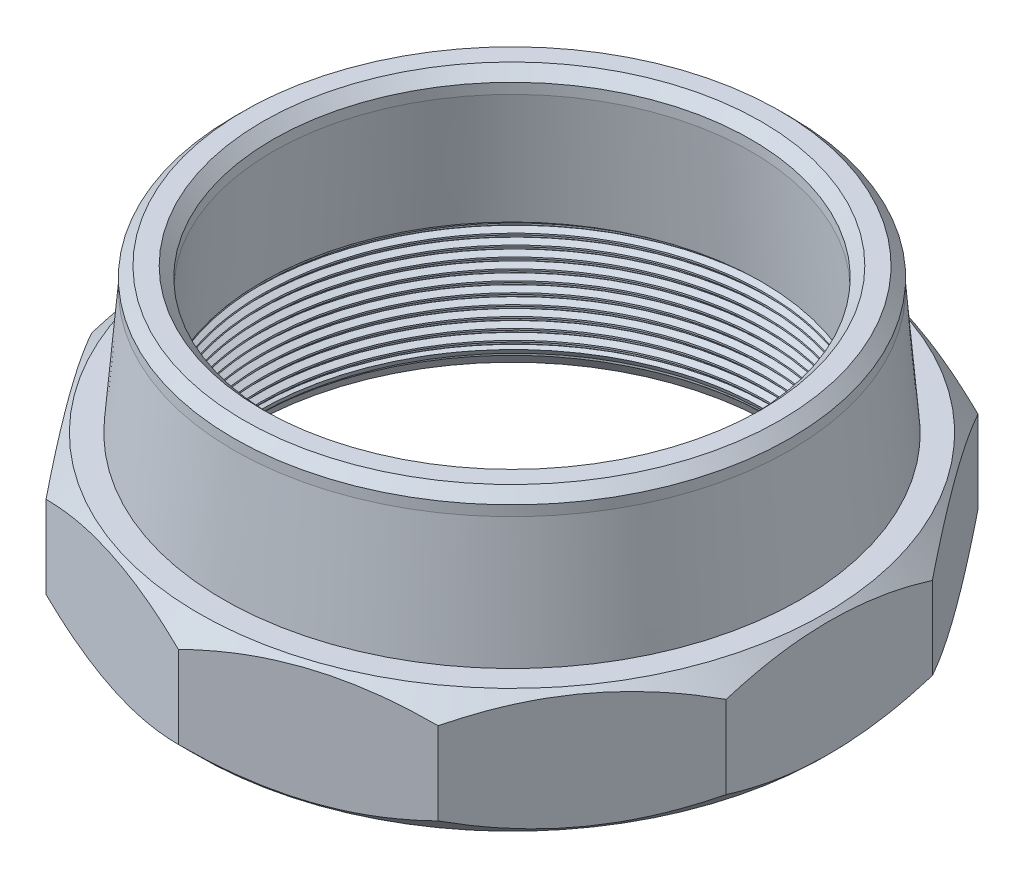
SolidWorks part; units mm, degrees
material "ABS"
ref_plane "Спереди" through (0, 0, 0) normal (0, 0, 1) x (1, 0, 0)
ref_plane "Сверху" through (0, 0, 0) normal (0, 1, 0) x (1, 0, 0)
ref_plane "Справа" through (0, 0, 0) normal (1, 0, 0) x (0, 0, -1)
sketch "Эскиз1" plane through (0, 0, 0) normal (0, 0, 1) x (1, 0, 0)
  line L0 (0, 9.0507) -> (0, -9.1503) construction
  line L1 (24.36, -12) -> (24.36, 0.6)
  line L3 (24.36, -12) -> (29.3544, -12)
  line L5 (28, 0) -> (27, 12.0447)
  line L9 (23.2, 14.0447) -> (27, 14.0447)
  line L10 (27, 14.0447) -> (27, 12.0447)
  line L11 (28, 0) -> (30.36, 0)
  line L12 (32.36, -2) -> (32.36, -10)
  line L13 (30.36, -12) -> (29.3544, -12)
  line L14 (30.36, 0) -> (32.36, -2)
  line L15 (32.36, -10) -> (30.36, -12)
  line L18 (24.2, 0.6) -> (23.2, 12.0301)
  line L19 (24.2, 0.6) -> (24.36, 0.6)
  line L20 (23.2, 12.0301) -> (23.2, 14.0447)
  dimension "D2" = 2
  dimension "D3" = 24.36
  dimension "D4" = 2
  dimension "D5" = 45
  dimension "D6" = 45
  dimension "D7" = 24.2
  dimension "D9" = 23.2
  dimension "D10" = 6
  dimension "D11" = 2
  dimension "D12" = 28
  dimension "D13" = 12.6
  dimension "D14" = 12
  dimension "D16" = 27
revolve "Повернуть1" add sketch "Эскиз1" angle 360 about L0
sketch "Эскиз2" plane through (0, 0, 0) normal (0, 1, 0) x (1, 0, 0)
  line L0 (0, 32.36) -> (0, -32.36) construction
  line L10 (0, 32.36) -> (-19.0207, 26.1798)
  line L11 (-19.0207, 26.1798) -> (-30.7762, 9.9998)
  line L12 (-30.7762, 9.9998) -> (-30.7762, -9.9998)
  line L13 (-30.7762, -9.9998) -> (-19.0207, -26.1798)
  line L14 (-19.0207, -26.1798) -> (0, -32.36)
  line L15 (0, -32.36) -> (19.0207, -26.1798)
  line L16 (19.0207, -26.1798) -> (30.7762, -9.9998)
  line L17 (30.7762, -9.9998) -> (30.7762, 9.9998)
  line L18 (30.7762, 9.9998) -> (19.0207, 26.1798)
  line L19 (19.0207, 26.1798) -> (0, 32.36)
  circle A0 centre (0, 0) radius 32.36 construction
  circle A1 centre (0, 0) radius 30.7762 construction
extrude "Вырез-Вытянуть3" cut sketch "Эскиз2" against normal blind 42 flip side to cut
chamfer "Фаска1" distance 2 distance2 1 1 edges at (-24.36, -12, 0) first distance on face at (-24.36, -12, 0)
chamfer "Фаска2" distance 1 angle 45 1 edges at (-27, 14.0447, 0)
sketch "Эскиз3" plane through (0, 0.6, 0) normal (0, -1, 0) x (1, 0, 0)
  circle A0 centre (0, 0) radius 24.36
  dimension "D1" = 48.72
curve "Спираль1" pitch 1 height 19.5 radius 24.36 left hand yes centre (0, 0.6, 0) axis (0, -1, 0) start towards (0, 0, 1)
ref_plane "Плоскость2" through (0, 0, 0) normal (-1, 0, 0) x (0, 0, 1)
sketch "Эскиз4" plane through (0, 0, 0) normal (-1, 0, 0) x (0, 0, 1)
  line L4 (-24.36, -19.325) -> (-24.36, -18.475) construction
  line L5 (-24.36, -18.475) -> (-24.8796, -18.775)
  line L6 (-24.8796, -18.775) -> (-24.8796, -19.025) construction
  line L7 (-24.8796, -19.025) -> (-24.36, -19.325)
  line L8 (-24.36, -18.9) -> (-24.8796, -18.9) construction
  line L9 (-24.8796, -18.775) -> (-24.9096, -18.775)
  line L10 (-24.9096, -18.775) -> (-24.9096, -19.025)
  line L11 (-24.9096, -19.025) -> (-24.8796, -19.025)
  line L12 (-24.36, -18.475) -> (-24.26, -18.4173)
  line L13 (-24.26, -18.4173) -> (-24.26, -19.3827)
  line L14 (-24.26, -19.3827) -> (-24.36, -19.325)
  line L15 (0, 0) -> (0, -30) construction
  spline S1 degree 3 poles (24.36, 0.6) (24.36, 0.5848) (23.6837, 0.5542) (20.7235, 0.5085) (16.0609, 0.4627) (10.0789, 0.4169) (3.2689, 0.3711) (-3.8097, 0.3254) (-10.5753, 0.2796) (-16.4721, 0.2338) (-21.0157, 0.188) (-23.8329, 0.1423) (-24.6921, 0.0965) (-23.5229, 0.0507) (-20.4212, 0.0049) (-15.6419, -0.0408) (-9.5776, -0.0866) (-2.7265, -0.1324) (4.3486, -0.1782) (11.0664, -0.2239) (16.8752, -0.2697) (21.2976, -0.3155) (23.9704, -0.3613) (24.674, -0.407) (23.3506, -0.4528) (20.1089, -0.4986) (15.2153, -0.5444) (9.0717, -0.5901) (2.1828, -0.6359) (-4.8853, -0.6817) (-11.5522, -0.7275) (-17.27, -0.7732) (-21.569, -0.819) (-24.0962, -0.8648) (-24.6438, -0.9106) (-23.1669, -0.9563) (-19.7868, -1.0021) (-14.7812, -1.0479) (-8.5613, -1.0937) (-1.6381, -1.1394) (5.4197, -1.1852) (12.0323, -1.231) (17.6564, -1.2768) (21.8299, -1.3225) (24.2102, -1.3683) (24.6015, -1.4141) (22.9718, -1.4599) (19.4549, -1.5056) (14.3398, -1.5514) (8.0467, -1.5972) (1.0925, -1.643) (-5.9515, -1.6887) (-12.5065, -1.7345) (-18.0341, -1.7803) (-22.0802, -1.8261) (-24.3123, -1.8718) (-24.5472, -1.9176) (-22.7655, -1.9634) (-19.1136, -2.0092) (-13.8915, -2.0549) (-7.5281, -2.1007) (-0.5464, -2.1465) (6.4803, -2.1923) (12.9746, -2.238) (18.403, -2.2838) (22.3196, -2.3296) (24.4026, -2.3754) (24.4809, -2.4211) (22.5481, -2.4669) (18.7629, -2.5127) (13.4363, -2.5585) (7.0059, -2.6042) (0, -2.65) (-7.0059, -2.6958) (-13.4363, -2.7415) (-18.7629, -2.7873) (-22.5481, -2.8331) (-24.4809, -2.8789) (-24.4026, -2.9246) (-22.3196, -2.9704) (-18.403, -3.0162) (-12.9746, -3.062) (-6.4803, -3.1077) (0.5464, -3.1535) (7.5281, -3.1993) (13.8915, -3.2451) (19.1136, -3.2908) (22.7655, -3.3366) (24.5472, -3.3824) (24.3123, -3.4282) (22.0802, -3.4739) (18.0341, -3.5197) (12.5065, -3.5655) (5.9515, -3.6113) (-1.0925, -3.657) (-8.0467, -3.7028) (-14.3398, -3.7486) (-19.4549, -3.7944) (-22.9718, -3.8401) (-24.6015, -3.8859) (-24.2102, -3.9317) (-21.8299, -3.9775) (-17.6564, -4.0232) (-12.0323, -4.069) (-5.4197, -4.1148) (1.6381, -4.1606) (8.5613, -4.2063) (14.7812, -4.2521) (19.7868, -4.2979) (23.1669, -4.3437) (24.6438, -4.3894) (24.0962, -4.4352) (21.569, -4.481) (17.27, -4.5268) (11.5522, -4.5725) (4.8853, -4.6183) (-2.1828, -4.6641) (-9.0717, -4.7099) (-15.2153, -4.7556) (-20.1089, -4.8014) (-23.3506, -4.8472) (-24.674, -4.893) (-23.9704, -4.9387) (-21.2976, -4.9845) (-16.8752, -5.0303) (-11.0664, -5.0761) (-4.3486, -5.1218) (2.7265, -5.1676) (9.5776, -5.2134) (15.6419, -5.2592) (20.4212, -5.3049) (23.5229, -5.3507) (24.6921, -5.3965) (23.8329, -5.4423) (21.0157, -5.488) (16.4721, -5.5338) (10.5753, -5.5796) (3.8097, -5.6254) (-3.2689, -5.6711) (-10.0789, -5.7169) (-16.0609, -5.7627) (-20.7235, -5.8085) (-23.6837, -5.8542) (-24.6982, -5.9) (-23.6837, -5.9458) (-20.7235, -5.9915) (-16.0609, -6.0373) (-10.0789, -6.0831) (-3.2689, -6.1289) (3.8097, -6.1746) (10.5753, -6.2204) (16.4721, -6.2662) (21.0157, -6.312) (23.8329, -6.3577) (24.6921, -6.4035) (23.5229, -6.4493) (20.4212, -6.4951) (15.6419, -6.5408) (9.5776, -6.5866) (2.7265, -6.6324) (-4.3486, -6.6782) (-11.0664, -6.7239) (-16.8752, -6.7697) (-21.2976, -6.8155) (-23.9704, -6.8613) (-24.674, -6.907) (-23.3506, -6.9528) (-20.1089, -6.9986) (-15.2153, -7.0444) (-9.0717, -7.0901) (-2.1828, -7.1359) (4.8853, -7.1817) (11.5522, -7.2275) (17.27, -7.2732) (21.569, -7.319) (24.0962, -7.3648) (24.6438, -7.4106) (23.1669, -7.4563) (19.7868, -7.5021) (14.7812, -7.5479) (8.5613, -7.5937) (1.6381, -7.6394) (-5.4197, -7.6852) (-12.0323, -7.731) (-17.6564, -7.7768) (-21.8299, -7.8225) (-24.2102, -7.8683) (-24.6015, -7.9141) (-22.9718, -7.9599) (-19.4549, -8.0056) (-14.3398, -8.0514) (-8.0467, -8.0972) (-1.0925, -8.143) (5.9515, -8.1887) (12.5065, -8.2345) (18.0341, -8.2803) (22.0802, -8.3261) (24.3123, -8.3718) (24.5472, -8.4176) (22.7655, -8.4634) (19.1136, -8.5092) (13.8915, -8.5549) (7.5281, -8.6007) (0.5464, -8.6465) (-6.4803, -8.6923) (-12.9746, -8.738) (-18.403, -8.7838) (-22.3196, -8.8296) (-24.4026, -8.8754) (-24.4809, -8.9211) (-22.5481, -8.9669) (-18.7629, -9.0127) (-13.4363, -9.0585) (-7.0059, -9.1042) (0, -9.15) (7.0059, -9.1958) (13.4363, -9.2415) (18.7629, -9.2873) (22.5481, -9.3331) (24.4809, -9.3789) (24.4026, -9.4246) (22.3196, -9.4704) (18.403, -9.5162) (12.9746, -9.562) (6.4803, -9.6077) (-0.5464, -9.6535) (-7.5281, -9.6993) (-13.8915, -9.7451) (-19.1136, -9.7908) (-22.7655, -9.8366) (-24.5472, -9.8824) (-24.3123, -9.9282) (-22.0802, -9.9739) (-18.0341, -10.0197) (-12.5065, -10.0655) (-5.9515, -10.1113) (1.0925, -10.157) (8.0467, -10.2028) (14.3398, -10.2486) (19.4549, -10.2944) (22.9718, -10.3401) (24.6015, -10.3859) (24.2102, -10.4317) (21.8299, -10.4775) (17.6564, -10.5232) (12.0323, -10.569) (5.4197, -10.6148) (-1.6381, -10.6606) (-8.5613, -10.7063) (-14.7812, -10.7521) (-19.7868, -10.7979) (-23.1669, -10.8437) (-24.6438, -10.8894) (-24.0962, -10.9352) (-21.569, -10.981) (-17.27, -11.0268) (-11.5522, -11.0725) (-4.8853, -11.1183) (2.1828, -11.1641) (9.0717, -11.2099) (15.2153, -11.2556) (20.1089, -11.3014) (23.3506, -11.3472) (24.674, -11.393) (23.9704, -11.4387) (21.2976, -11.4845) (16.8752, -11.5303) (11.0664, -11.5761) (4.3486, -11.6218) (-2.7265, -11.6676) (-9.5776, -11.7134) (-15.6419, -11.7592) (-20.4212, -11.8049) (-23.5229, -11.8507) (-24.6921, -11.8965) (-23.8329, -11.9423) (-21.0157, -11.988) (-16.4721, -12.0338) (-10.5753, -12.0796) (-3.8097, -12.1254) (3.2689, -12.1711) (10.0789, -12.2169) (16.0609, -12.2627) (20.7235, -12.3085) (23.6837, -12.3542) (24.6982, -12.4) (23.6837, -12.4458) (20.7235, -12.4915) (16.0609, -12.5373) (10.0789, -12.5831) (3.2689, -12.6289) (-3.8097, -12.6746) (-10.5753, -12.7204) (-16.4721, -12.7662) (-21.0157, -12.812) (-23.8329, -12.8577) (-24.6921, -12.9035) (-23.5229, -12.9493) (-20.4212, -12.9951) (-15.6419, -13.0408) (-9.5776, -13.0866) (-2.7265, -13.1324) (4.3486, -13.1782) (11.0664, -13.2239) (16.8752, -13.2697) (21.2976, -13.3155) (23.9704, -13.3613) (24.674, -13.407) (23.3506, -13.4528) (20.1089, -13.4986) (15.2153, -13.5444) (9.0717, -13.5901) (2.1828, -13.6359) (-4.8853, -13.6817) (-11.5522, -13.7275) (-17.27, -13.7732) (-21.569, -13.819) (-24.0962, -13.8648) (-24.6438, -13.9106) (-23.1669, -13.9563) (-19.7868, -14.0021) (-14.7812, -14.0479) (-8.5613, -14.0937) (-1.6381, -14.1394) (5.4197, -14.1852) (12.0323, -14.231) (17.6564, -14.2768) (21.8299, -14.3225) (24.2102, -14.3683) (24.6015, -14.4141) (22.9718, -14.4599) (19.4549, -14.5056) (14.3398, -14.5514) (8.0467, -14.5972) (1.0925, -14.643) (-5.9515, -14.6887) (-12.5065, -14.7345) (-18.0341, -14.7803) (-22.0802, -14.8261) (-24.3123, -14.8718) (-24.5472, -14.9176) (-22.7655, -14.9634) (-19.1136, -15.0092) (-13.8915, -15.0549) (-7.5281, -15.1007) (-0.5464, -15.1465) (6.4803, -15.1923) (12.9746, -15.238) (18.403, -15.2838) (22.3196, -15.3296) (24.4026, -15.3754) (24.4809, -15.4211) (22.5481, -15.4669) (18.7629, -15.5127) (13.4363, -15.5585) (7.0059, -15.6042) (0, -15.65) (-7.0059, -15.6958) (-13.4363, -15.7415) (-18.7629, -15.7873) (-22.5481, -15.8331) (-24.4809, -15.8789) (-24.4026, -15.9246) (-22.3196, -15.9704) (-18.403, -16.0162) (-12.9746, -16.062) (-6.4803, -16.1077) (0.5464, -16.1535) (7.5281, -16.1993) (13.8915, -16.2451) (19.1136, -16.2908) (22.7655, -16.3366) (24.5472, -16.3824) (24.3123, -16.4282) (22.0802, -16.4739) (18.0341, -16.5197) (12.5065, -16.5655) (5.9515, -16.6113) (-1.0925, -16.657) (-8.0467, -16.7028) (-14.3398, -16.7486) (-19.4549, -16.7944) (-22.9718, -16.8401) (-24.6015, -16.8859) (-24.2102, -16.9317) (-21.8299, -16.9775) (-17.6564, -17.0232) (-12.0323, -17.069) (-5.4197, -17.1148) (1.6381, -17.1606) (8.5613, -17.2063) (14.7812, -17.2521) (19.7868, -17.2979) (23.1669, -17.3437) (24.6438, -17.3894) (24.0962, -17.4352) (21.569, -17.481) (17.27, -17.5268) (11.5522, -17.5725) (4.8853, -17.6183) (-2.1828, -17.6641) (-9.0717, -17.7099) (-15.2153, -17.7556) (-20.1089, -17.8014) (-23.3506, -17.8472) (-24.674, -17.893) (-23.9704, -17.9387) (-21.2976, -17.9845) (-16.8752, -18.0303) (-11.0664, -18.0761) (-4.3486, -18.1218) (2.7265, -18.1676) (9.5776, -18.2134) (15.6419, -18.2592) (20.4212, -18.3049) (23.5229, -18.3507) (24.6921, -18.3965) (23.8329, -18.4423) (21.0157, -18.488) (16.4721, -18.5338) (10.5753, -18.5796) (3.8097, -18.6254) (-3.2689, -18.6711) (-10.0789, -18.7169) (-16.0609, -18.7627) (-20.7235, -18.8085) (-23.6837, -18.8542) (-24.36, -18.8848) (-24.36, -18.9) knots 0 0 0 0 0.002347 0.004695 0.007042 0.00939 0.011737 0.014085 0.016432 0.018779 0.021127 0.023474 0.025822 0.028169 0.030516 0.032864 0.035211 0.037559 0.039906 0.042254 0.044601 0.046948 0.049296 0.051643 0.053991 0.056338 0.058685 0.061033 0.06338 0.065728 0.068075 0.070423 0.07277 0.075117 0.077465 0.079812 0.08216 0.084507 0.086854 0.089202 0.091549 0.093897 0.096244 0.098592 0.100939 0.103286 0.105634 0.107981 0.110329 0.112676 0.115023 0.117371 0.119718 0.122066 0.124413 0.126761 0.129108 0.131455 0.133803 0.13615 0.138498 0.140845 0.143192 0.14554 0.147887 0.150235 0.152582 0.15493 0.157277 0.159624 0.161972 0.164319 0.166667 0.169014 0.171362 0.173709 0.176056 0.178404 0.180751 0.183099 0.185446 0.187793 0.190141 0.192488 0.194836 0.197183 0.199531 0.201878 0.204225 0.206573 0.20892 0.211268 0.213615 0.215962 0.21831 0.220657 0.223005 0.225352 0.2277 0.230047 0.232394 0.234742 0.237089 0.239437 0.241784 0.244131 0.246479 0.248826 0.251174 0.253521 0.255869 0.258216 0.260563 0.262911 0.265258 0.267606 0.269953 0.2723 0.274648 0.276995 0.279343 0.28169 0.284038 0.286385 0.288732 0.29108 0.293427 0.295775 0.298122 0.300469 0.302817 0.305164 0.307512 0.309859 0.312207 0.314554 0.316901 0.319249 0.321596 0.323944 0.326291 0.328638 0.330986 0.333333 0.335681 0.338028 0.340376 0.342723 0.34507 0.347418 0.349765 0.352113 0.35446 0.356808 0.359155 0.361502 0.36385 0.366197 0.368545 0.370892 0.373239 0.375587 0.377934 0.380282 0.382629 0.384977 0.387324 0.389671 0.392019 0.394366 0.396714 0.399061 0.401408 0.403756 0.406103 0.408451 0.410798 0.413146 0.415493 0.41784 0.420188 0.422535 0.424883 0.42723 0.429577 0.431925 0.434272 0.43662 0.438967 0.441315 0.443662 0.446009 0.448357 0.450704 0.453052 0.455399 0.457746 0.460094 0.462441 0.464789 0.467136 0.469484 0.471831 0.474178 0.476526 0.478873 0.481221 0.483568 0.485915 0.488263 0.49061 0.492958 0.495305 0.497653 0.5 0.502347 0.504695 0.507042 0.50939 0.511737 0.514085 0.516432 0.518779 0.521127 0.523474 0.525822 0.528169 0.530516 0.532864 0.535211 0.537559 0.539906 0.542254 0.544601 0.546948 0.549296 0.551643 0.553991 0.556338 0.558685 0.561033 0.56338 0.565728 0.568075 0.570423 0.57277 0.575117 0.577465 0.579812 0.58216 0.584507 0.586854 0.589202 0.591549 0.593897 0.596244 0.598592 0.600939 0.603286 0.605634 0.607981 0.610329 0.612676 0.615023 0.617371 0.619718 0.622066 0.624413 0.626761 0.629108 0.631455 0.633803 0.63615 0.638498 0.640845 0.643192 0.64554 0.647887 0.650235 0.652582 0.65493 0.657277 0.659624 0.661972 0.664319 0.666667 0.669014 0.671362 0.673709 0.676056 0.678404 0.680751 0.683099 0.685446 0.687793 0.690141 0.692488 0.694836 0.697183 0.699531 0.701878 0.704225 0.706573 0.70892 0.711268 0.713615 0.715962 0.71831 0.720657 0.723005 0.725352 0.7277 0.730047 0.732394 0.734742 0.737089 0.739437 0.741784 0.744131 0.746479 0.748826 0.751174 0.753521 0.755869 0.758216 0.760563 0.762911 0.765258 0.767606 0.769953 0.7723 0.774648 0.776995 0.779343 0.78169 0.784038 0.786385 0.788732 0.79108 0.793427 0.795775 0.798122 0.800469 0.802817 0.805164 0.807512 0.809859 0.812207 0.814554 0.816901 0.819249 0.821596 0.823944 0.826291 0.828638 0.830986 0.833333 0.835681 0.838028 0.840376 0.842723 0.84507 0.847418 0.849765 0.852113 0.85446 0.856808 0.859155 0.861502 0.86385 0.866197 0.868545 0.870892 0.873239 0.875587 0.877934 0.880282 0.882629 0.884977 0.887324 0.889671 0.892019 0.894366 0.896714 0.899061 0.901408 0.903756 0.906103 0.908451 0.910798 0.913146 0.915493 0.91784 0.920188 0.922535 0.924883 0.92723 0.929577 0.931925 0.934272 0.93662 0.938967 0.941315 0.943662 0.946009 0.948357 0.950704 0.953052 0.955399 0.957746 0.960094 0.962441 0.964789 0.967136 0.969484 0.971831 0.974178 0.976526 0.978873 0.981221 0.983568 0.985915 0.988263 0.99061 0.992958 0.995305 0.997653 1 1 1 1 construction
  dimension "D1" = 0.85
  dimension "D2" = 0.25
  dimension "D3" = 60
  dimension "D4" = 0.03
  dimension "D5" = 0.1
sweep "Вырез-По траектории1" cut profiles "Эскиз4" path "Спираль1" align with end faces yes
chamfer "Фаска3" distance 1 angle 45 1 edges at (-23.2, 14.0447, 0)
